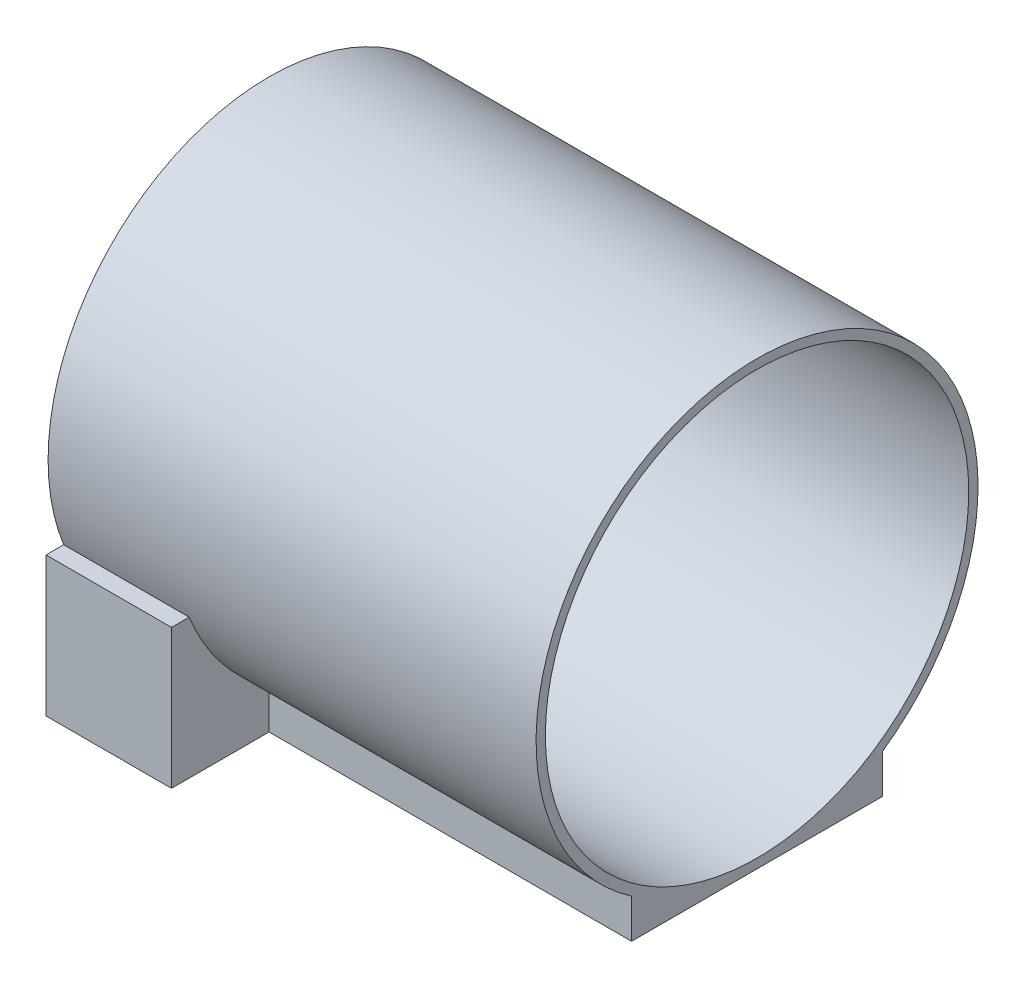
SolidWorks part; units mm, degrees
ref_plane "Front Plane" through (0, 0, 0) normal (0, 0, 1) x (1, 0, 0)
ref_plane "Top Plane" through (0, 0, 0) normal (0, 1, 0) x (1, 0, 0)
ref_plane "Right Plane" through (0, 0, 0) normal (1, 0, 0) x (0, 0, -1)
sketch "Sketch2" plane through (0, 0, 0) normal (0, 1, 0) x (1, 0, 0)
  line L0 (0, 75) -> (0, -75) construction
  line L1 (-125, -75) -> (-115, -75)
  line L2 (-125, -75) -> (-125, 75)
  line L3 (-125, 75) -> (-115, 75)
  line L4 (125, -75) -> (125, 75)
  line L5 (-125, -75) -> (125, 75) construction
  line L6 (-125, 75) -> (125, -75) construction
  line L7 (-125, 0) -> (125, 0) construction
  line L8 (115, 48) -> (47, 48)
  line L10 (-115, 75) -> (-115, 48)
  line L11 (-115, 48) -> (-47, 48)
  line L12 (-47, 75) -> (-47, 48)
  line L17 (47, 75) -> (47, 48)
  line L19 (115, 75) -> (115, 48)
  line L20 (115, -75) -> (115, -48)
  line L22 (47, -75) -> (47, -48)
  line L23 (115, -48) -> (47, -48)
  line L24 (-115, -48) -> (-47, -48)
  line L25 (-47, -75) -> (-47, -48)
  line L27 (-115, -75) -> (-115, -48)
  line L28 (-47, 75) -> (47, 75)
  line L29 (115, 75) -> (125, 75)
  line L30 (115, -75) -> (125, -75)
  line L31 (-47, -75) -> (47, -75)
  line L32 (-125, 75) -> (125, 75) construction
  line L34 (-115, -43) -> (-105, -43)
  line L35 (-115, -43) -> (-115, 43)
  line L36 (-115, 43) -> (-105, 43)
  line L37 (-105, -43) -> (-105, 43)
  line L38 (-115, -43) -> (-105, 43) construction
  line L39 (-115, 43) -> (-105, -43) construction
  point P0 (0, 0)
  point P26 (-110, 0)
  dimension "D1" = 150
  dimension "D2" = 250
  dimension "D3" = 10
  dimension "D4" = 68
  dimension "D5" = 27
  dimension "D6" = 10
  dimension "D7" = 5
extrude "Boss-Extrude1" add sketch "Sketch2" along normal blind 10
sketch "Sketch3" plane through (0, 10, 0) normal (0, 1, 0) x (1, 0, 0)
  line L0 (-115, 43) -> (-105, 43)
  line L1 (-105, 43) -> (-105, -43)
  line L2 (-105, -43) -> (-115, -43)
  line L3 (-115, -43) -> (-115, 43)
  line L4 (-115, 48) -> (-47, 48) construction
  line L5 (-47, 48) -> (-47, 75)
  line L6 (-47, 75) -> (47, 75)
  line L7 (47, 75) -> (47, 48)
  line L8 (93, 48) -> (115, 48)
  line L9 (115, 48) -> (115, 75)
  line L10 (115, 75) -> (125, 75)
  line L11 (125, 75) -> (125, -75)
  line L12 (125, -75) -> (115, -75)
  line L13 (115, -75) -> (115, -48)
  line L14 (115, -48) -> (93, -48)
  line L15 (47, -48) -> (47, -75)
  line L16 (47, -75) -> (-47, -75)
  line L17 (-47, -75) -> (-47, -48)
  line L18 (-93, -48) -> (-115, -48)
  line L19 (-115, -75) -> (-115, -48) construction
  line L20 (-115, -48) -> (-47, -48) construction
  line L21 (-115, -48) -> (-115, -75)
  line L22 (-115, -75) -> (-125, -75)
  line L23 (-125, -75) -> (-125, 75)
  line L24 (-125, 75) -> (-115, 75)
  line L25 (-115, 75) -> (-115, 48)
  line L26 (-81, 48) -> (-81, 75) construction
  line L27 (-93, 48) -> (-93, 27)
  line L28 (-93, 27) -> (-26, 27)
  line L29 (-26, 27) -> (-26, 48)
  line L30 (-26, 48) -> (-47, 48)
  line L31 (-115, 48) -> (-93, 48)
  line L32 (-125, 0) -> (125, 0) construction
  line L33 (0, -75) -> (0, 75) construction
  line L34 (26, 48) -> (47, 48)
  line L35 (26, 27) -> (26, 48)
  line L36 (93, 27) -> (26, 27)
  line L37 (93, 48) -> (93, 27)
  line L38 (93, -48) -> (93, -27)
  line L39 (26, -48) -> (47, -48)
  line L40 (93, -27) -> (26, -27)
  line L41 (26, -27) -> (26, -48)
  line L42 (-26, -27) -> (-26, -48)
  line L43 (-26, -48) -> (-47, -48)
  line L44 (-93, -48) -> (-93, -27)
  line L45 (-93, -27) -> (-26, -27)
  dimension "D1" = 12
  dimension "D2" = 67
  dimension "D3" = 21
extrude "Boss-Extrude2" add sketch "Sketch3" along normal blind 23
sketch "Sketch4" plane through (-105, 0, 0) normal (-1, 0, 0) x (0, 0, 1)
  line L0 (-43, 0) -> (-9.2235, 14.7039)
  line L1 (-9.2235, 14.7039) -> (-43, 33)
  line L2 (0, 33) -> (0, 0) construction
  line L3 (-75, 33) -> (75, 33) construction
  line L4 (43, 0) -> (9.2235, 14.7039)
  line L5 (9.2235, 14.7039) -> (-24.5529, 33)
  line L6 (-43, 0) -> (-43, 33)
  line L7 (43, 0) -> (43, 33)
  line L8 (43, 33) -> (-24.5529, 33)
extrude "Boss-Extrude3" add sketch "Sketch4" along normal up to next
sketch "Sketch5" plane through (-115, 0, 0) normal (1, 0, 0) x (0, 0, -1)
  line L0 (24.5529, 33) -> (43, 33) construction
  circle A0 centre (0, 80.55) radius 47.55
  dimension "D1" = 95.1
extrude "Boss-Extrude4" add sketch "Sketch5" along normal blind 100 and the other way blind 5 separate body
sketch "Sketch7" plane through (0, 33, 0) normal (0, 1, 0) x (1, 0, 0)
  line L0 (-120, 0) -> (-120, 48)
  line L1 (-120, 47.55) -> (-120, -47.55) construction
  line L2 (-120, 48) -> (-93, 48)
  line L3 (-93, 48) -> (-93, 27)
  line L4 (-93, 27) -> (-93, 48) construction
  line L5 (-93, 27) -> (-93, 48) construction
  line L6 (-93, 27) -> (-15, 27)
  line L7 (-15, -47.55) -> (-15, 47.55) construction
  line L8 (-15, 27) -> (-15, -27)
  line L9 (-15, -27) -> (-93, -27)
  line L10 (-93, -27) -> (-93, -48)
  line L11 (-93, -48) -> (-120, -48)
  line L12 (-120, -48) -> (-120, 0)
  line L14 (-105, 43) -> (-115, 43) construction
  line L16 (-105, 43) -> (-115, 43)
  line L17 (-115, 43) -> (-115, 24.5529)
  line L18 (-115, 24.5529) -> (-105, 24.5529)
  line L19 (-105, 24.5529) -> (-105, 43)
extrude "Boss-Extrude6" add sketch "Sketch7" along normal blind 30
sketch "Sketch8" plane through (-105, 0, 0) normal (-1, 0, 0) x (0, 0, 1)
  line L0 (-43, 46.6261) -> (-41.8716, 62.212)
  line L1 (-43, 60.2522) -> (-43, 33) construction
  line L3 (-41.8716, 62.212) -> (26.3558, 62.212) construction
  line L6 (-24.5529, 33) -> (-24.5529, 62.212)
  line L7 (-24.5529, 62.212) -> (-41.8716, 62.212)
  line L8 (-43, 46.6261) -> (-43, 33)
  line L9 (-43, 33) -> (-24.5529, 33)
  line L10 (-43.8716, 62.212) -> (-41.8716, 62.212) construction
  arc A0 (-43, 60.2522) -> (-24.5529, 39.8295) centre (0, 80.55) ccw construction
  dimension "D1" = 2
extrude "Cut-Extrude2" cut sketch "Sketch8" along normal blind 10 contours L0 L7 L6 L9 L8
sketch "Sketch9" plane through (-105, 0, 0) normal (-1, 0, 0) x (0, 0, 1)
  line L0 (-42.1389, 58.5202) -> (-43, 46.6261)
  line L1 (-43, 60.2522) -> (-43, 33) construction
  line L2 (-43, 46.6261) -> (-43, 62.212)
  line L3 (-43, 62.212) -> (-41.8716, 62.212)
  line L4 (-42.1389, 58.5202) -> (-41.8716, 62.212)
extrude "Boss-Extrude7" add sketch "Sketch9" along normal up to next
sketch "Sketch6" plane through (-15, 0, 0) normal (1, 0, 0) x (0, 0, -1)
  line L0 (0, 128.1) -> (0, 33) construction
  circle A0 centre (0, 80.55) radius 47.55 construction
  circle A1 centre (0, 80.55) radius 45.55
  dimension "D1" = 2
extrude "Cut-Extrude1" cut sketch "Sketch6" against normal blind 100
sketch "Sketch10" plane through (0, 33, 0) normal (0, 1, 0) x (1, 0, 0)
  line L0 (0, 0) -> (125, 0) construction
  line L1 (125, -75) -> (125, 75) construction
  line L2 (5, 34) -> (20, 34)
  line L3 (5, -44) -> (20, -44)
  line L4 (5, -44) -> (5, -34)
  line L5 (5, -34) -> (20, -34)
  line L6 (20, -44) -> (20, -34)
  line L7 (20, 44) -> (20, 34)
  line L8 (5, 44) -> (20, 44)
  line L9 (5, 44) -> (5, 34)
  line L10 (-47, -75) -> (47, -75) construction
  line L11 (-15, -47.55) -> (-15, 47.55) construction
  line L13 (58, -7.5) -> (68, -7.5)
  line L14 (58, -7.5) -> (58, 7.5)
  line L15 (58, 7.5) -> (68, 7.5)
  line L16 (68, -7.5) -> (68, 7.5)
  line L17 (58, -7.5) -> (68, 7.5) construction
  line L18 (58, 7.5) -> (68, -7.5) construction
  point P17 (63, 0)
  dimension "D1" = 41
  dimension "D2" = 10
  dimension "D3" = 15
  dimension "D4" = 20
  dimension "D5" = 67
extrude "Boss-Extrude8" add sketch "Sketch10" along normal blind 28.5
fillet "Fillet1" radius 30 1 edges at (12.5, 33, 44)
fillet "Fillet2" radius 30 1 edges at (12.5, 33, -44)
fillet "Fillet3" radius 30 1 edges at (68, 33, 0)
sketch "Sketch11" plane through (0, 0, 75) normal (0, 0, 1) x (1, 0, 0)
  line L1 (-125, 33) -> (125, 33)
  line L2 (-125, 33) -> (-125, 0)
  line L3 (-125, 0) -> (125, 0)
  line L4 (125, 33) -> (125, 0)
extrude "Cut-Extrude3" cut sketch "Sketch11" against normal through all
delete or keep bodies "Body-Delete/Keep 1" type delete bodies bodies 111
delete or keep bodies "Body-Delete/Keep 2" type delete bodies bodies 112
delete or keep bodies "Body-Delete/Keep 3" type delete bodies bodies 113
